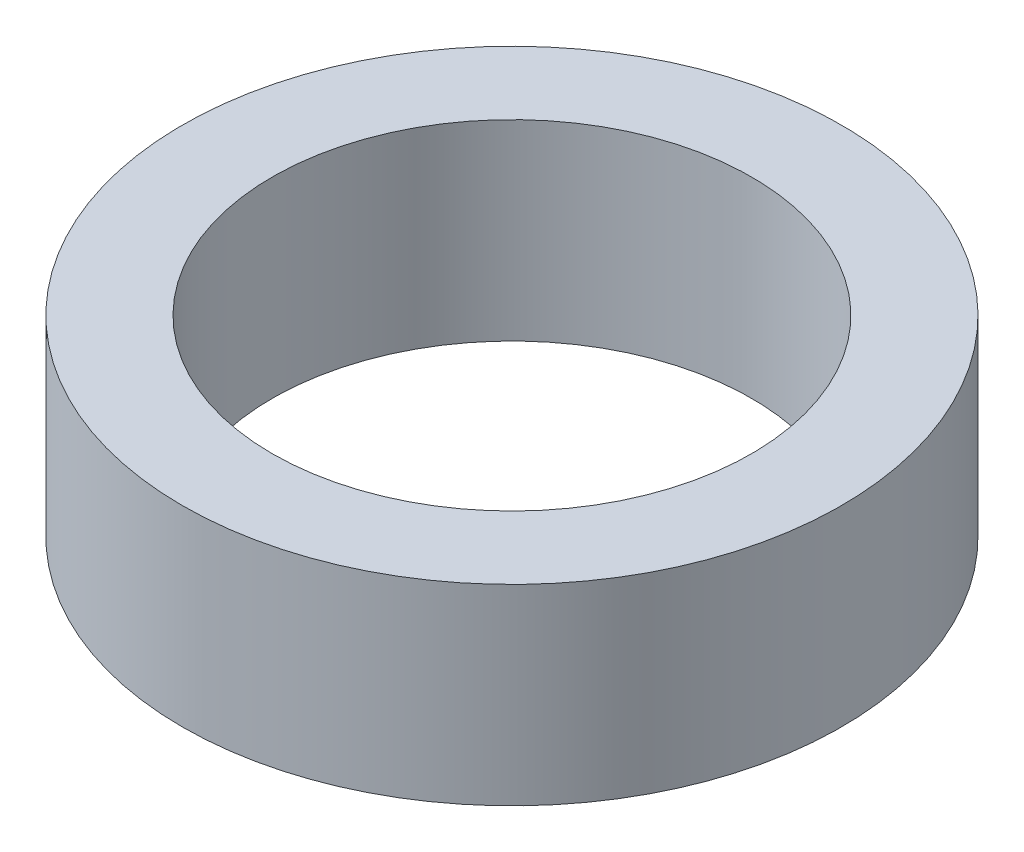
SolidWorks part; units mm, degrees
ref_plane "Front Plane" through (0, 0, 0) normal (0, 0, 1) x (1, 0, 0)
ref_plane "Top Plane" through (0, 0, 0) normal (0, 1, 0) x (1, 0, 0)
ref_plane "Right Plane" through (0, 0, 0) normal (1, 0, 0) x (0, 0, -1)
sketch "Sketch1" plane through (0, 0, 0) normal (0, 1, 0) x (1, 0, 0)
  circle A0 centre (0, 0) radius 27.5
  dimension "FLANGE_OD" = 55
extrude "Boss-Extrude1" add sketch "Sketch1" along normal blind 16
sketch "Sketch2" plane through (0, 0, 0) normal (0, 1, 0) x (1, 0, 0)
  circle A0 centre (0, 0) radius 20
  dimension "BORE_D" = 40
extrude "Cut-Extrude1" cut sketch "Sketch2" along normal through all
sketch "Sketch3" plane through (0, 16, 0) normal (0, 1, 0) x (1, 0, 0)
  circle A0 centre (0, 0) radius 11.4452 construction
  circle A1 centre (-11.4452, 0) radius 1.5
  dimension "BOLT_D" = 3
  dimension "BOLT_PCD" = 22.8905
extrude "Cut-Extrude2" cut sketch "Sketch3" against normal blind 10.7841 rebuild error yes
pattern_circular "CirPattern1" count 3 over 360 rebuild error yes
